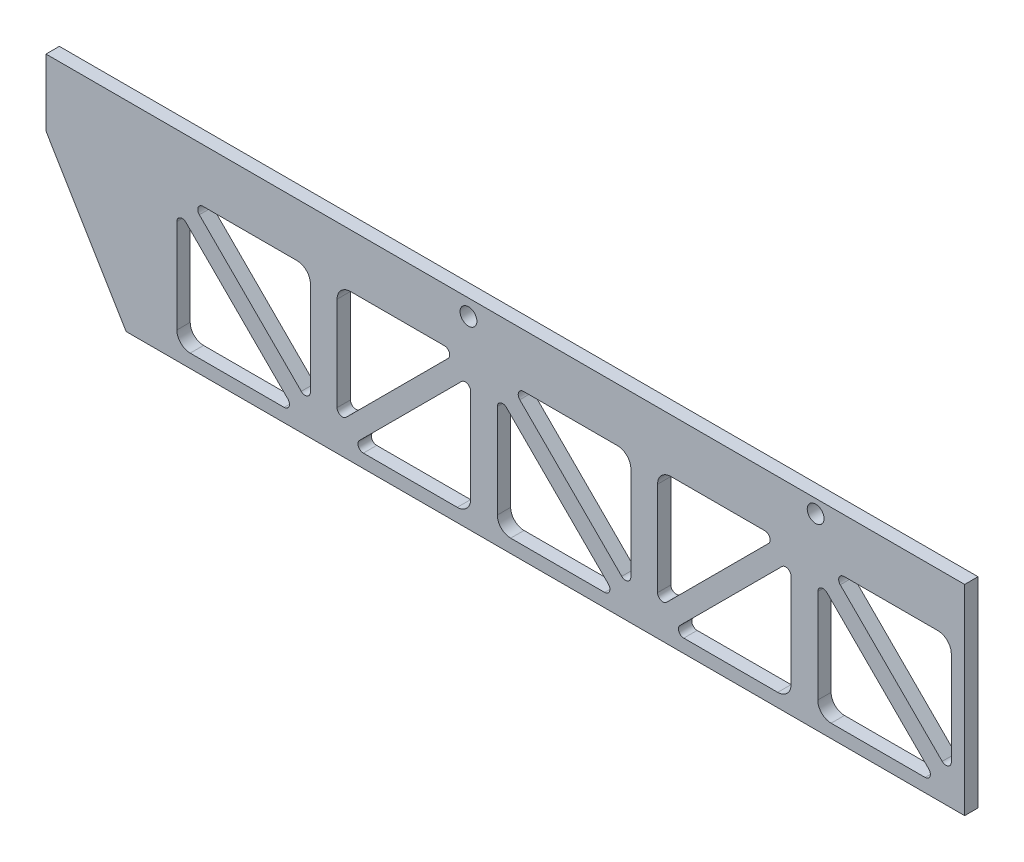
SolidWorks part; units mm, degrees
material "Balsa"
ref_plane "Front Plane" through (0, 0, 0) normal (0, 0, 1) x (1, 0, 0)
ref_plane "Top Plane" through (0, 0, 0) normal (0, 1, 0) x (1, 0, 0)
ref_plane "Right Plane" through (0, 0, 0) normal (1, 0, 0) x (0, 0, -1)
sketch "Model" plane through (0, 0, 0) normal (0, 0, 1) x (1, 0, 0)
  line L8 (-171.2321, 6.35) -> (-215.9, 6.35)
  line L9 (-222.25, 57.3679) -> (-222.25, 12.7)
  line L10 (-217.9139, 59.1639) -> (-169.4361, 10.6861)
  line L11 (-234.95, 57.3679) -> (-234.95, 12.7)
  line L12 (-241.3, 6.35) -> (-285.9679, 6.35)
  line L13 (-239.2861, 59.1639) -> (-287.7639, 10.6861)
  line L14 (-294.1139, 17.0361) -> (-245.6361, 65.5139)
  line L15 (-298.45, 63.5) -> (-298.45, 18.8321)
  line L16 (-247.4321, 69.85) -> (-292.1, 69.85)
  line L17 (-323.6321, 6.35) -> (-368.3, 6.35)
  line L18 (-374.65, 57.3679) -> (-374.65, 12.7)
  line L19 (-370.3139, 59.1639) -> (-321.8361, 10.6861)
  line L20 (-18.8321, 6.35) -> (-63.5, 6.35)
  line L21 (-69.85, 57.3679) -> (-69.85, 12.7)
  line L22 (-17.0361, 10.6861) -> (-65.5139, 59.1639)
  line L23 (-82.55, 57.3679) -> (-82.55, 12.7)
  line L24 (-88.9, 6.35) -> (-133.5679, 6.35)
  line L25 (-86.8861, 59.1639) -> (-135.3639, 10.6861)
  line L26 (-93.2361, 65.5139) -> (-141.7139, 17.0361)
  line L27 (-146.05, 63.5) -> (-146.05, 18.8321)
  line L28 (-95.0321, 69.85) -> (-139.7, 69.85)
  line L29 (-163.0861, 17.0361) -> (-211.5639, 65.5139)
  line L30 (-165.1, 69.85) -> (-209.7679, 69.85)
  line L31 (-158.75, 63.5) -> (-158.75, 18.8321)
  line L32 (-315.4861, 17.0361) -> (-363.9639, 65.5139)
  line L33 (-317.5, 69.85) -> (-362.1679, 69.85)
  line L34 (-311.15, 63.5) -> (-311.15, 18.8321)
  line L35 (-398.78, 0) -> (-436.88, 63.5)
  line L36 (0, 0) -> (-398.78, 0)
  line L37 (0, 0) -> (0, 95.25)
  line L38 (0, 95.25) -> (-436.88, 95.25)
  line L39 (-436.88, 63.5) -> (-436.88, 95.25)
  line L40 (-6.35, 63.5) -> (-6.35, 18.8321)
  line L41 (-59.1639, 65.5139) -> (-10.6861, 17.0361)
  line L42 (-12.7, 69.85) -> (-57.3679, 69.85)
  arc A0 (-222.25, 12.7) -> (-215.9, 6.35) centre (-215.9, 12.7) ccw
  arc A1 (-217.9139, 59.1639) -> (-222.25, 57.3679) centre (-219.71, 57.3679) ccw
  arc A2 (-171.2321, 6.35) -> (-169.4361, 10.6861) centre (-171.2321, 8.89) ccw
  arc A3 (-234.95, 57.3679) -> (-239.2861, 59.1639) centre (-237.49, 57.3679) ccw
  arc A4 (-241.3, 6.35) -> (-234.95, 12.7) centre (-241.3, 12.7) ccw
  arc A5 (-287.7639, 10.6861) -> (-285.9679, 6.35) centre (-285.9679, 8.89) ccw
  arc A6 (-245.6361, 65.5139) -> (-247.4321, 69.85) centre (-247.4321, 67.31) ccw
  arc A7 (-298.45, 18.8321) -> (-294.1139, 17.0361) centre (-295.91, 18.8321) ccw
  arc A8 (-292.1, 69.85) -> (-298.45, 63.5) centre (-292.1, 63.5) ccw
  arc A9 (-323.6321, 6.35) -> (-321.8361, 10.6861) centre (-323.6321, 8.89) ccw
  arc A10 (-374.65, 12.7) -> (-368.3, 6.35) centre (-368.3, 12.7) ccw
  arc A11 (-370.3139, 59.1639) -> (-374.65, 57.3679) centre (-372.11, 57.3679) ccw
  arc A12 (-69.85, 12.7) -> (-63.5, 6.35) centre (-63.5, 12.7) ccw
  arc A13 (-65.5139, 59.1639) -> (-69.85, 57.3679) centre (-67.31, 57.3679) ccw
  arc A14 (-18.8321, 6.35) -> (-17.0361, 10.6861) centre (-18.8321, 8.89) ccw
  arc A15 (-82.55, 57.3679) -> (-86.8861, 59.1639) centre (-85.09, 57.3679) ccw
  arc A16 (-88.9, 6.35) -> (-82.55, 12.7) centre (-88.9, 12.7) ccw
  arc A17 (-135.3639, 10.6861) -> (-133.5679, 6.35) centre (-133.5679, 8.89) ccw
  arc A18 (-93.2361, 65.5139) -> (-95.0321, 69.85) centre (-95.0321, 67.31) ccw
  arc A19 (-146.05, 18.8321) -> (-141.7139, 17.0361) centre (-143.51, 18.8321) ccw
  arc A20 (-139.7, 69.85) -> (-146.05, 63.5) centre (-139.7, 63.5) ccw
  arc A21 (-163.0861, 17.0361) -> (-158.75, 18.8321) centre (-161.29, 18.8321) ccw
  arc A22 (-209.7679, 69.85) -> (-211.5639, 65.5139) centre (-209.7679, 67.31) ccw
  arc A23 (-158.75, 63.5) -> (-165.1, 69.85) centre (-165.1, 63.5) ccw
  arc A24 (-362.1679, 69.85) -> (-363.9639, 65.5139) centre (-362.1679, 67.31) ccw
  arc A25 (-311.15, 63.5) -> (-317.5, 69.85) centre (-317.5, 63.5) ccw
  arc A26 (-315.4861, 17.0361) -> (-311.15, 18.8321) centre (-313.69, 18.8321) ccw
  arc A27 (-10.6861, 17.0361) -> (-6.35, 18.8321) centre (-8.89, 18.8321) ccw
  arc A28 (-57.3679, 69.85) -> (-59.1639, 65.5139) centre (-57.3679, 67.31) ccw
  arc A29 (-6.35, 63.5) -> (-12.7, 69.85) centre (-12.7, 63.5) ccw
  circle A30 centre (-70.866, 88.9) radius 4
  circle A31 centre (-235.966, 87.63) radius 4
  dimension "D2" = 70.866
  dimension "D4" = 8
  dimension "D5" = 165.1
  dimension "D7" = 8
  dimension "D1" = 95.25
  dimension "D3" = 6.35
  dimension "D6" = 7.62
extrude "Boss-Extrude1" add sketch "Model" along normal blind 6.35
equation "\"thick\"=0.25"
equation "\"D1@Boss-Extrude1\"=\"thick\""
